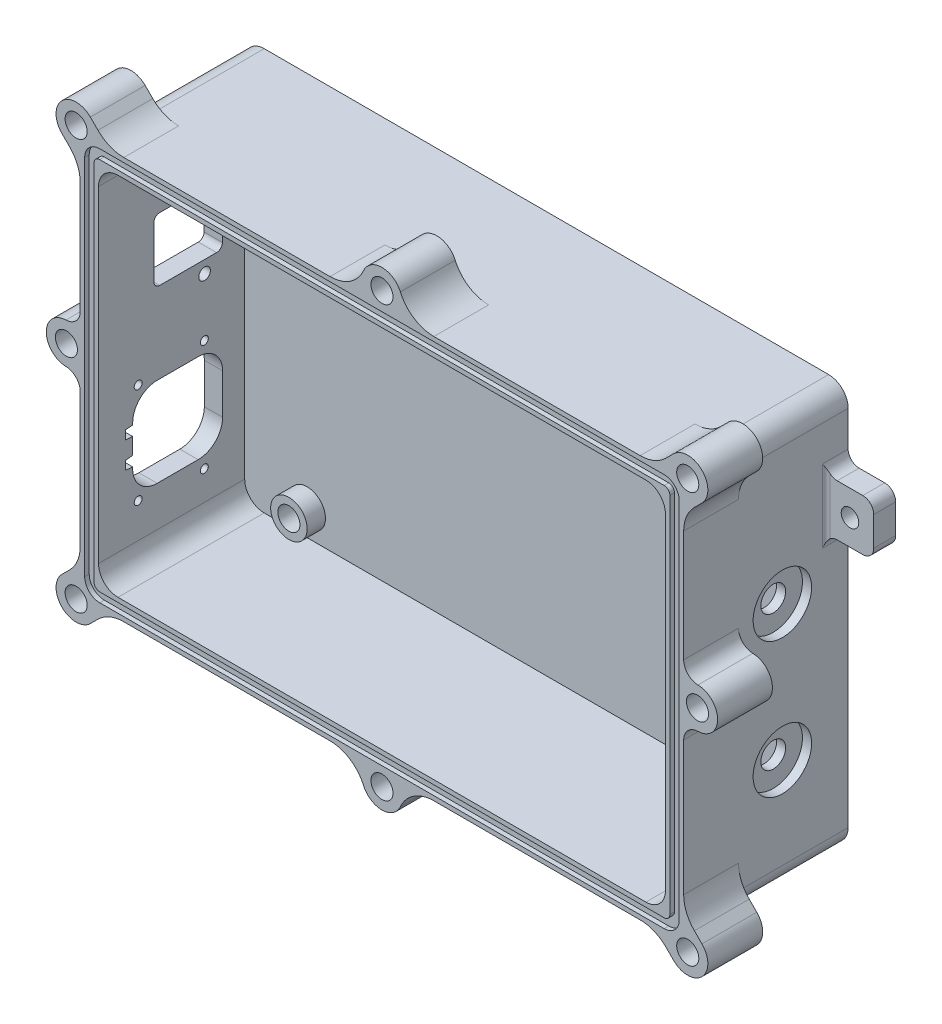
SolidWorks part; units mm, degrees
material "Custom Plastic"
ref_plane "X-Y Datum" through (0, 0, 0) normal (0, 0, 1) x (1, 0, 0)
ref_plane "X-Z Datum" through (0, 0, 0) normal (0, 1, 0) x (1, 0, 0)
ref_plane "Y-Z Datum" through (0, 0, 0) normal (1, 0, 0) x (0, 0, -1)
sketch "Sketch1" plane through (0, 0, 0) normal (0, 0, 1) x (1, 0, 0)
  line L1 (-82.55, 55) -> (82.55, 55)
  line L2 (-82.55, 55) -> (-82.55, -55)
  line L3 (-82.55, -55) -> (82.55, -55)
  line L4 (82.55, 55) -> (82.55, -55)
  line L5 (-82.55, 55) -> (82.55, -55) construction
  line L6 (-82.55, -55) -> (82.55, 55) construction
  point P0 (0, 0)
  dimension "D1" = 165.1
  dimension "D2" = 110
extrude "Boss-Extrude1" add sketch "Sketch1" along normal blind 45
shell "Shell1" thickness 5 removed face at (0, 0, 45)
fillet "Fillet1" radius 5.334 8 edges at (-77.55, -50, 25) (-82.55, -55, 22.5) (82.55, -55, 22.5) (77.55, -50, 25) (82.55, 55, 22.5) (77.55, 50, 25) (-82.55, 55, 22.5) (-77.55, 50, 25)
sketch "Sketch2" plane through (0, 0, 45) normal (0, 0, 1) x (1, 0, 0)
  line L20 (-77.216, -53.7827) -> (77.216, -53.7827)
  line L21 (81.3327, -49.666) -> (81.3327, 49.666)
  line L22 (77.216, 53.7827) -> (-77.216, 53.7827)
  line L23 (-81.3327, 49.666) -> (-81.3327, -49.666)
  line L24 (-77.216, -52.5) -> (77.216, -52.5)
  line L25 (80.05, -49.666) -> (80.05, 49.666)
  line L26 (77.216, 52.5) -> (-77.216, 52.5)
  line L27 (-80.05, 49.666) -> (-80.05, -49.666)
  line L28 (-77.216, -52.5) -> (77.216, -52.5) construction
  line L29 (80.05, -49.666) -> (80.05, 49.666) construction
  line L30 (77.216, 52.5) -> (-77.216, 52.5) construction
  line L31 (-80.05, 49.666) -> (-80.05, -49.666) construction
  line L32 (-78.7673, 49.666) -> (-78.7673, -49.666)
  line L33 (-77.216, -51.2173) -> (77.216, -51.2173)
  line L34 (78.7673, -49.666) -> (78.7673, 49.666)
  line L35 (77.216, 51.2173) -> (-77.216, 51.2173)
  arc A16 (77.216, -53.7827) -> (81.3327, -49.666) centre (77.216, -49.666) ccw
  arc A17 (81.3327, 49.666) -> (77.216, 53.7827) centre (77.216, 49.666) ccw
  arc A18 (-77.216, 53.7827) -> (-81.3327, 49.666) centre (-77.216, 49.666) ccw
  arc A19 (-81.3327, -49.666) -> (-77.216, -53.7827) centre (-77.216, -49.666) ccw
  arc A20 (-80.05, -49.666) -> (-77.216, -52.5) centre (-77.216, -49.666) ccw
  arc A21 (77.216, -52.5) -> (80.05, -49.666) centre (77.216, -49.666) ccw
  arc A22 (80.05, 49.666) -> (77.216, 52.5) centre (77.216, 49.666) ccw
  arc A23 (-77.216, 52.5) -> (-80.05, 49.666) centre (-77.216, 49.666) ccw
  arc A24 (-80.05, -49.666) -> (-77.216, -52.5) centre (-77.216, -49.666) ccw construction
  arc A25 (77.216, -52.5) -> (80.05, -49.666) centre (77.216, -49.666) ccw construction
  arc A26 (80.05, 49.666) -> (77.216, 52.5) centre (77.216, 49.666) ccw construction
  arc A27 (-77.216, 52.5) -> (-80.05, 49.666) centre (-77.216, 49.666) ccw construction
  arc A28 (-77.216, 51.2173) -> (-78.7673, 49.666) centre (-77.216, 49.666) ccw
  arc A29 (-78.7673, -49.666) -> (-77.216, -51.2173) centre (-77.216, -49.666) ccw
  arc A30 (77.216, -51.2173) -> (78.7673, -49.666) centre (77.216, -49.666) ccw
  arc A31 (78.7673, 49.666) -> (77.216, 51.2173) centre (77.216, 49.666) ccw
  dimension "D1" = 2.5
  dimension "D2" = 1.2827
  dimension "D3" = 1.2827
extrude "Cut-Extrude1" cut sketch "Sketch2" against normal blind 1.2446
sketch "Sketch3" plane through (0, 0, 45) normal (0, 0, 1) x (1, 0, 0)
  line L0 (77.216, 49.666) -> (80.9877, 53.4377)
  line L1 (80.9877, 53.4377) -> (83.6625, 56.1125)
  line L2 (79.7734, 60.0016) -> (74.7718, 55)
  line L3 (77.216, 55) -> (-77.216, 55) construction
  line L4 (82.55, -49.666) -> (82.55, 49.666) construction
  line L5 (82.55, -49.666) -> (82.55, 49.666)
  line L6 (77.216, 55) -> (-77.216, 55)
  line L7 (87.5516, 52.2234) -> (82.55, 47.2218)
  arc A0 (82.55, 49.666) -> (77.216, 55) centre (77.216, 49.666) ccw construction
  circle A1 centre (83.6625, 56.1125) radius 3.025
  circle A2 centre (83.6625, 56.1125) radius 5.5
  arc A3 (81.3327, 49.666) -> (77.216, 53.7827) centre (77.216, 49.666) ccw construction
  arc A4 (82.55, 49.666) -> (77.216, 55) centre (77.216, 49.666) ccw
  point P10 (80.1269, 52.5769)
  arc M15 (82.55, 49.666) -> (77.216, 55) centre (77.216, 49.666) ccw
  line M16 (77.216, 55) -> (-77.216, 55)
  dimension "D1" = 6.05
  dimension "D2" = 11
  dimension "D3" = 5
extrude "Boss-Extrude2" add sketch "Sketch3" against normal blind 15 contours A2 L5 L7 M15 | A2 A1 M15 | A2 L2 M16 M15 | A1 region at (82.5376, 58.8282, 45) region at (79.824, 54.4965, 45) region at (77.1925, 56.331, 45) region at (83.881, 49.6425, 45)
sketch "Sketch4" plane through (0, 0, 45) normal (0, 0, 1) x (1, 0, 0)
  line L0 (87.5516, 52.2234) -> (82.55, 47.2218) construction
  line L1 (79.7734, 60.0016) -> (74.7718, 55) construction
  line L2 (77.216, 49.666) -> (80.9877, 53.4377) construction
  line L3 (80.9877, 53.4377) -> (83.6625, 56.1125) construction
  line L4 (82.55, -49.666) -> (82.55, 49.666) construction
  line L5 (77.216, 55) -> (-77.216, 55) construction
  line L6 (87.5516, 52.2234) -> (82.55, 47.2218)
  line L7 (79.7734, 60.0016) -> (74.7718, 55)
  line L8 (77.216, 49.666) -> (80.9877, 53.4377)
  line L9 (80.9877, 53.4377) -> (83.6625, 56.1125)
  line L10 (82.55, -49.666) -> (82.55, 49.666)
  line L11 (77.216, 55) -> (-77.216, 55)
  arc A0 (82.55, 49.666) -> (77.216, 55) centre (77.216, 49.666) ccw construction
  circle A1 centre (83.6625, 56.1125) radius 5.5
  circle A2 centre (83.6625, 56.1125) radius 5.5
  circle A3 centre (83.6625, 56.1125) radius 3.025
  circle A4 centre (83.6625, 56.1125) radius 3.025
  arc A5 (82.55, 49.666) -> (77.216, 55) centre (77.216, 49.666) ccw
  dimension "D1" = 0
  dimension "D2" = 0
extrude "Cut-Extrude2" cut sketch "Sketch4" against normal blind 8 contours A4 region at (82.5376, 58.8282, 45)
mirror "Mirror2" about plane through (0, 0, 0) normal (0, 1, 0) of "Cut-Extrude2", "Boss-Extrude2"
mirror "Mirror3" about plane through (0, 0, 0) normal (1, 0, 0) of "Mirror2"
fillet "Fillet3" radius 10 8 edges at (82.55, 47.2218, 37.5) (74.7718, 55, 37.5) (-74.7718, 55, 37.5) (-82.55, 47.2218, 37.5) (-82.55, -47.2218, 37.5) (-74.7718, -55, 37.5) (74.7718, -55, 37.5) (82.55, -47.2218, 37.5)
sketch "Sketch5" plane through (0, 0, 45) normal (0, 0, 1) x (1, 0, 0)
  line L1 (0, -55) -> (0, -58.7827)
  line L2 (-70.6297, -55) -> (70.6297, -55) construction
  line L3 (-77.216, -53.7827) -> (77.216, -53.7827) construction
  line L4 (-5.5, -58.7827) -> (-5.5, -55)
  line L5 (5.5, -58.7827) -> (5.5, -55)
  line L6 (-70.6297, -55) -> (70.6297, -55)
  circle A0 centre (0, -58.7827) radius 3.025
  circle A1 centre (0, -58.7827) radius 5.5
  line M18 (-70.6297, -55) -> (70.6297, -55)
  dimension "D1" = 6.05
  dimension "D2" = 11
  dimension "D3" = 5
extrude "Boss-Extrude3" add sketch "Sketch5" against normal blind 15 contours A0 | A1 A0 L6 M18 | A1 L5 L6 | A1 L4 M18 region at (2.0785, -56.7042, 45) region at (1.9963, -55.1439, 45) region at (-5.0608, -55.9178, 45) region at (5.0608, -55.9178, 45)
sketch "Sketch6" plane through (0, 0, 45) normal (0, 0, 1) x (1, 0, 0)
  line L0 (-70.6297, -55) -> (70.6297, -55) construction
  line L1 (5.5, -58.7827) -> (5.5, -55) construction
  line L2 (-5.5, -58.7827) -> (-5.5, -55) construction
  line L3 (0, -55) -> (0, -58.7827) construction
  line L4 (-70.6297, -55) -> (70.6297, -55)
  line L5 (5.5, -58.7827) -> (5.5, -55)
  line L6 (-5.5, -58.7827) -> (-5.5, -55)
  line L7 (0, -55) -> (0, -58.7827)
  circle A1 centre (0, -58.7827) radius 5.5
  circle A2 centre (0, -58.7827) radius 5.5
  circle A3 centre (0, -58.7827) radius 3.025
  circle A4 centre (0, -58.7827) radius 3.025
  dimension "D1" = 0
  dimension "D2" = 0
extrude "Cut-Extrude3" cut sketch "Sketch6" against normal blind 8 contours A4 region at (2.0785, -56.7042, 45)
mirror "Mirror10" about plane through (0, 0, 0) normal (0, 1, 0) of "Cut-Extrude3", "Boss-Extrude3"
fillet "Fillet5" radius 10 4 edges at (5.5, 55, 37.5) (-5.5, 55, 37.5) (-5.5, -55, 37.5) (5.5, -55, 37.5)
sketch "Sketch7" plane through (0, 0, 45) normal (0, 0, 1) x (1, 0, 0)
  line L0 (-82.55, 3.0797) -> (-86.3327, 3.0797)
  line L2 (-82.55, 43.0797) -> (-82.55, -43.0797) construction
  line L3 (-81.3327, 49.666) -> (-81.3327, -49.666) construction
  line L4 (-86.3327, 8.5797) -> (-82.55, 8.5797)
  line L5 (-86.3327, -2.4203) -> (-82.55, -2.4203)
  line L6 (-82.55, 43.0797) -> (-82.55, -43.0797)
  circle A0 centre (-86.3327, 3.0797) radius 3.025
  circle A1 centre (-86.3327, 3.0797) radius 5.5
  line M18 (-82.55, 43.0797) -> (-82.55, -43.0797)
  dimension "D1" = 6.05
  dimension "D2" = 11
  dimension "D3" = 5
  dimension "D4" = 40
extrude "Boss-Extrude4" add sketch "Sketch7" against normal blind 15 contours A1 L4 M18 | A1 L5 L6 | L6 A1 A0 M18 | A0 region at (-89.2721, 3.0797, 45) region at (-82.6939, 1.0834, 45) region at (-83.4678, 8.1405, 45) region at (-83.4678, -1.9811, 45)
sketch "Sketch8" plane through (0, 0, 45) normal (0, 0, 1) x (1, 0, 0)
  line L0 (-78.7673, 49.666) -> (-78.7673, -49.666) construction
  line L1 (-82.55, 43.0797) -> (-82.55, -43.0797) construction
  line L2 (-86.3327, -2.4203) -> (-82.55, -2.4203) construction
  line L3 (-86.3327, 8.5797) -> (-82.55, 8.5797) construction
  line L4 (-82.55, 3.0797) -> (-86.3327, 3.0797) construction
  line L5 (-82.55, 43.0797) -> (-82.55, -43.0797)
  line L6 (-86.3327, -2.4203) -> (-82.55, -2.4203)
  line L7 (-86.3327, 8.5797) -> (-82.55, 8.5797)
  line L8 (-82.55, 3.0797) -> (-86.3327, 3.0797)
  circle A1 centre (-86.3327, 3.0797) radius 5.5
  circle A2 centre (-86.3327, 3.0797) radius 5.5
  circle A3 centre (-86.3327, 3.0797) radius 3.025
  circle A4 centre (-86.3327, 3.0797) radius 3.025
  point P0 (-78.7673, 0)
  dimension "D1" = 0
  dimension "D2" = 0
extrude "Cut-Extrude4" cut sketch "Sketch8" against normal blind 8 contours A4 region at (-89.2721, 3.0797, 45)
mirror "Mirror11" about plane through (0, 0, 0) normal (1, 0, 0) of "Cut-Extrude4", "Boss-Extrude4"
fillet "Fillet6" radius 4 4 edges at (82.55, 8.5797, 37.5) (82.55, -2.4203, 37.5) (-82.55, 8.5797, 37.5) (-82.55, -2.4203, 37.5)
sketch "Sketch9" plane through (0, 0, 5) normal (0, 0, 1) x (1, 0, 0)
  circle A0 centre (-60.455, 42.799) radius 3.025
  circle A1 centre (50.035, 12.954) radius 3.025
  circle A2 centre (50.035, -42.926) radius 3.025
  circle A3 centre (-60.455, -42.926) radius 3.025
  circle A4 centre (-60.455, -42.926) radius 5
  circle A5 centre (50.035, -42.926) radius 5
  circle A6 centre (50.035, 12.954) radius 5
  circle A7 centre (-60.455, 42.799) radius 5
  point P0 (-60.455, 42.799)
  point P1 (50.035, 12.954)
  point P3 (50.035, -42.926)
  point P5 (-60.455, -42.926)
  dimension "D1" = 6.05
  dimension "D2" = 10
extrude "Boss-Extrude5" add sketch "Sketch9" along normal blind 5
sketch "Sketch10" plane through (0, 0, 0) normal (0, 0, -1) x (-1, 0, 0)
  line L0 (70.6297, -55) -> (14.1984, -55) construction
  line L1 (50.55, -55) -> (64.55, -55)
  line L2 (50.55, -55) -> (50.55, -68)
  line L3 (50.55, -68) -> (64.55, -68)
  line L4 (64.55, -55) -> (64.55, -68)
  line L15 (-82.55, 12.5772) -> (-82.55, 43.0797) construction
  line L16 (-82.55, 37) -> (-95.55, 37)
  line L17 (-82.55, 37) -> (-82.55, 23)
  line L18 (-82.55, 23) -> (-95.55, 23)
  line L19 (-95.55, 37) -> (-95.55, 23)
  line L20 (-95.55, 23) -> (-82.55, 37) construction
  line L21 (50.55, -68) -> (64.55, -55) construction
  line L22 (-70.6297, 55) -> (-14.1984, 55) construction
  line L23 (82.55, -6.4178) -> (82.55, -43.0797) construction
  circle A0 centre (-89.05, 30) radius 2 construction
  circle A1 centre (57.55, -61.5) radius 2 construction
  dimension "D1" = 4
  dimension "D4" = 4
  dimension "D2" = 14
  dimension "D3" = 13
  dimension "D5" = 25
  dimension "D6" = 25
extrude "Boss-Extrude6" add sketch "Sketch10" against normal blind 6
hole_wizard "M4 Clearance Hole1" positions "Sketch13" profile "Sketch12" hole size "M4" standard "ANSI Metric" end condition through all
sketch "Sketch13" plane through (0, 0, 6) normal (0, 0, 1) x (1, 0, 0)
  point P0 (-57.55, -61.5)
  point P3 (89.05, 30)
sketch "Sketch12" plane through (-57.55, -61.5, 6) normal (1, 0, 0) x (0, -1, 0)
  line L0 (0, 0) -> (0, 6)
  line L1 (0, 6) -> (2.4, 6)
  line L2 (2.4, 6) -> (2.4, 0)
  line L5 (2.4, 0) -> (0, 0)
  line L11 (0, -6.35) -> (0, 107.95) construction
  dimension "Thru Hole Dia." = 4.8
  dimension "Thru Hole Depth" = 6
fillet "Fillet7" radius 3 8 edges at (-50.55, -55, 3) (-64.55, -55, 3) (-64.55, -68, 3) (-50.55, -68, 3) (95.55, 37, 3) (95.55, 23, 3) (82.55, 23, 3) (82.55, 37, 3)
fillet "Fillet8" radius 1 2 edges at (-57.55, -55, 6) (82.55, 30, 6)
sketch "Sketch14" plane through (-82.55, 0, 0) normal (-1, 0, 0) x (0, 0, 1)
  line L0 (37.1425, -18.606) -> (37.1425, -17.1559) construction
  line L1 (37.1425, -25.806) -> (37.1425, -24.3559) construction
  line L2 (28.9425, -9.781) -> (17.7425, -9.781) construction
  line L3 (11.5425, -15.981) -> (11.5425, -26.981) construction
  line L4 (17.7425, -33.181) -> (28.9425, -33.181) construction
  line L5 (35.1425, -26.981) -> (35.1425, -25.981) construction
  line L6 (35.282, -25.9688) -> (37.1425, -25.806) construction
  line L7 (34.837, -26.0077) -> (35.282, -25.9688) construction
  line L8 (35.282, -24.1931) -> (37.1425, -24.3559) construction
  line L9 (35.1425, -24.181) -> (35.1425, -18.781) construction
  line L10 (34.837, -18.8077) -> (35.282, -18.7688) construction
  line L11 (35.282, -18.7688) -> (37.1425, -18.606) construction
  line L12 (35.282, -16.9931) -> (37.1425, -17.1559) construction
  line L13 (35.1425, -16.981) -> (35.1425, -15.981) construction
  line L14 (37.1425, -18.606) -> (37.1425, -17.1559) construction
  line L15 (37.1425, -25.806) -> (37.1425, -24.3559) construction
  line L16 (28.9425, -9.781) -> (17.7425, -9.781) construction
  line L17 (11.5425, -15.981) -> (11.5425, -26.981) construction
  line L18 (17.7425, -33.181) -> (28.9425, -33.181) construction
  line L19 (35.1425, -26.981) -> (35.1425, -25.981) construction
  line L20 (35.282, -25.9688) -> (37.1425, -25.806) construction
  line L21 (34.837, -26.0077) -> (35.282, -25.9688) construction
  line L22 (35.282, -24.1931) -> (37.1425, -24.3559) construction
  line L23 (35.1425, -24.181) -> (35.1425, -18.781) construction
  line L24 (34.837, -18.8077) -> (35.282, -18.7688) construction
  line L25 (35.282, -18.7688) -> (37.1425, -18.606) construction
  line L26 (35.282, -16.9931) -> (37.1425, -17.1559) construction
  line L27 (35.1425, -16.981) -> (35.1425, -15.981) construction
  line L28 (34.8806, -19.3058) -> (35.3255, -19.2669)
  line L29 (35.3255, -19.2669) -> (37.6425, -19.0641)
  line L30 (37.6425, -19.0641) -> (37.6425, -16.6978)
  line L31 (35.3264, -16.4951) -> (37.6425, -16.6978)
  line L32 (34.8806, -26.5058) -> (35.3255, -26.4669)
  line L33 (35.3255, -26.4669) -> (37.6425, -26.2641)
  line L34 (37.6425, -26.2641) -> (37.6425, -23.8978)
  line L35 (35.3264, -23.6951) -> (37.6425, -23.8978)
  line L36 (35.6425, -16.981) -> (35.6425, -15.981)
  line L37 (28.9425, -9.281) -> (17.7425, -9.281)
  line L38 (11.0425, -15.981) -> (11.0425, -26.981)
  line L39 (17.7425, -33.681) -> (28.9425, -33.681)
  line L40 (35.6425, -26.981) -> (35.6425, -25.981)
  line L41 (35.6425, -24.181) -> (35.6425, -18.781)
  line L42 (28.2478, 29.611) -> (12.6978, 29.611) construction
  line L43 (11.5978, 28.511) -> (11.5978, 14.461) construction
  line L44 (12.6978, 13.361) -> (28.2478, 13.361) construction
  line L45 (29.3478, 14.461) -> (29.3478, 28.511) construction
  line L46 (28.2478, 29.611) -> (12.6978, 29.611) construction
  line L47 (11.5978, 28.511) -> (11.5978, 14.461) construction
  line L48 (12.6978, 13.361) -> (28.2478, 13.361) construction
  line L49 (29.3478, 14.461) -> (29.3478, 28.511) construction
  line L50 (16.9728, 9.486) -> (14.9728, 9.486) construction
  line L51 (25.9728, 33.486) -> (23.9728, 33.486) construction
  line L52 (28.2478, 30.111) -> (12.6978, 30.111)
  line L53 (11.0978, 28.511) -> (11.0978, 14.461)
  line L54 (12.6978, 12.861) -> (28.2478, 12.861)
  line L55 (29.8478, 14.461) -> (29.8478, 28.511)
  spline S0 degree 3 poles (17.7425, -9.781) (14.1107, -9.781) (11.5425, -12.3491) (11.5425, -15.981) knots 0 0 0 0 1 1 1 1 weights 1 0.804738 0.804738 1 construction
  spline S1 degree 3 poles (11.5425, -26.981) (11.5425, -30.6128) (14.1107, -33.181) (17.7425, -33.181) knots 0 0 0 0 1 1 1 1 weights 1 0.804738 0.804738 1 construction
  spline S2 degree 3 poles (28.9425, -33.181) (32.5744, -33.181) (35.1425, -30.6128) (35.1425, -26.981) knots 0 0 0 0 1 1 1 1 weights 1 0.804738 0.804738 1 construction
  spline S3 degree 3 poles (2026.1511, -214.6767) (16.8817, -22.4202) (37.0242, -24.3539) (35.1725, -24.1831) (35.0836, -24.1753) (30.4685, -23.7841) (6.3657, -21.3606) (2023.9813, -231.7948) knots -14.295266 -14.295266 -14.295266 -14.295266 0.151076 0.326628 0.526648 0.751115 27.466708 27.466708 27.466708 27.466708 only from (35.282, -24.1931) to (34.837, -24.1542) construction
  spline S4 degree 3 poles (2026.1511, -207.4767) (16.8817, -15.2202) (37.0242, -17.1539) (35.1725, -16.9831) (35.0836, -16.9753) (30.4685, -16.5841) (6.3657, -14.1606) (2023.9813, -224.5948) knots -14.295266 -14.295266 -14.295266 -14.295266 0.151076 0.326628 0.526648 0.751115 27.466708 27.466708 27.466708 27.466708 only from (35.282, -16.9931) to (34.837, -16.9542) construction
  spline S5 degree 3 poles (35.1425, -15.981) (35.1425, -12.3491) (32.5744, -9.781) (28.9425, -9.781) knots 0 0 0 0 1 1 1 1 weights 1 0.804738 0.804738 1 construction
  spline S6 degree 3 poles (17.7425, -9.781) (14.1107, -9.781) (11.5425, -12.3491) (11.5425, -15.981) knots 0 0 0 0 1 1 1 1 weights 1 0.804738 0.804738 1 construction
  spline S7 degree 3 poles (11.5425, -26.981) (11.5425, -30.6128) (14.1107, -33.181) (17.7425, -33.181) knots 0 0 0 0 1 1 1 1 weights 1 0.804738 0.804738 1 construction
  spline S8 degree 3 poles (28.9425, -33.181) (32.5744, -33.181) (35.1425, -30.6128) (35.1425, -26.981) knots 0 0 0 0 1 1 1 1 weights 1 0.804738 0.804738 1 construction
  spline S9 degree 3 poles (35.282, -24.1931) (35.2682, -24.1919) (35.2383, -24.1892) (35.1725, -24.1831) (35.0836, -24.1753) (34.9691, -24.1656) (34.8825, -24.1581) (34.837, -24.1542) knots 0 0 0 0 0.151076 0.326628 0.526648 0.751115 1 1 1 1 construction
  spline S10 degree 3 poles (35.282, -16.9931) (35.2682, -16.9919) (35.2383, -16.9892) (35.1725, -16.9831) (35.0836, -16.9753) (34.9691, -16.9656) (34.8825, -16.9581) (34.837, -16.9542) knots 0 0 0 0 0.151076 0.326628 0.526648 0.751115 1 1 1 1 construction
  spline S11 degree 3 poles (35.1425, -15.981) (35.1425, -12.3491) (32.5744, -9.781) (28.9425, -9.781) knots 0 0 0 0 1 1 1 1 weights 1 0.804738 0.804738 1 construction
  spline S12 degree 1 poles (35.3264, -16.4951) (34.8799, -16.4561) knots 0 0 1 1 construction
  spline S13 degree 3 poles (35.3264, -16.4951) (35.3004, -16.4928) (35.2564, -16.4887) (35.1419, -16.4784) (35.0167, -16.4678) (34.9248, -16.4599) (34.8799, -16.4561) knots 0.00312 0.00312 0.00312 0.00312 0.25234 0.50156 0.75078 1 1 1 1
  spline S14 degree 1 poles (35.3264, -23.6951) (34.8799, -23.6561) knots 0 0 1 1 construction
  spline S15 degree 3 poles (35.3264, -23.6951) (35.3004, -23.6928) (35.2564, -23.6887) (35.1419, -23.6784) (35.0167, -23.6678) (34.9248, -23.6599) (34.8799, -23.6561) knots 0.00312 0.00312 0.00312 0.00312 0.25234 0.50156 0.75078 1 1 1 1
  spline S16 degree 1 poles (35.6425, -15.981) (28.9425, -9.281) knots 0 0 1 1 construction
  spline S17 degree 1 poles (17.7425, -9.281) (11.0425, -15.981) knots 0 0 1 1 construction
  spline S18 degree 1 poles (11.0425, -26.981) (17.7425, -33.681) knots 0 0 1 1 construction
  spline S19 degree 1 poles (28.9425, -33.681) (35.6425, -26.981) knots 0 0 1 1 construction
  spline S20 degree 3 poles (35.6425, -15.981) (35.6425, -15.5729) (35.5721, -14.773) (35.1002, -13.0836) (33.8203, -11.1032) (31.8399, -9.8233) (30.1505, -9.3514) (29.3506, -9.281) (28.9425, -9.281) knots 0 0 0 0 0.125 0.25 0.5 0.75 0.875 1 1 1 1
  spline S21 degree 3 poles (17.7425, -9.281) (17.3345, -9.281) (16.5346, -9.3514) (14.8452, -9.8233) (12.8648, -11.1032) (11.5849, -13.0836) (11.113, -14.773) (11.0425, -15.5729) (11.0425, -15.981) knots 0 0 0 0 0.125 0.25 0.5 0.75 0.875 1 1 1 1
  spline S22 degree 3 poles (11.0425, -26.981) (11.0425, -27.389) (11.113, -28.1889) (11.5849, -29.8783) (12.8648, -31.8587) (14.8452, -33.1386) (16.5346, -33.6105) (17.3345, -33.681) (17.7425, -33.681) knots 0 0 0 0 0.125 0.25 0.5 0.75 0.875 1 1 1 1
  spline S23 degree 3 poles (28.9425, -33.681) (29.3506, -33.681) (30.1505, -33.6105) (31.8399, -33.1386) (33.8203, -31.8587) (35.1002, -29.8783) (35.5721, -28.1889) (35.6425, -27.389) (35.6425, -26.981) knots 0 0 0 0 0.125 0.25 0.5 0.75 0.875 1 1 1 1
  spline S24 degree 3 poles (23.9728, 33.486) (23.9728, 31.486) (25.9728, 31.486) (25.9728, 33.486) knots 0 0 0 0 1 1 1 1 weights 1 0.333333 0.333333 1 construction
  spline S25 degree 3 poles (25.9728, 33.486) (25.9728, 35.486) (23.9728, 35.486) (23.9728, 33.486) knots 0 0 0 0 1 1 1 1 weights 1 0.333333 0.333333 1 construction
  spline S26 degree 3 poles (23.9728, 33.486) (23.9728, 31.486) (25.9728, 31.486) (25.9728, 33.486) knots 0 0 0 0 1 1 1 1 weights 1 0.333333 0.333333 1 construction
  spline S27 degree 3 poles (25.9728, 33.486) (25.9728, 35.486) (23.9728, 35.486) (23.9728, 33.486) knots 0 0 0 0 1 1 1 1 weights 1 0.333333 0.333333 1 construction
  spline S28 degree 3 poles (16.9728, 9.486) (16.9728, 11.486) (14.9728, 11.486) (14.9728, 9.486) knots 0 0 0 0 1 1 1 1 weights 1 0.333333 0.333333 1 construction
  spline S29 degree 3 poles (14.9728, 9.486) (14.9728, 7.486) (16.9728, 7.486) (16.9728, 9.486) knots 0 0 0 0 1 1 1 1 weights 1 0.333333 0.333333 1 construction
  spline S30 degree 3 poles (16.9728, 9.486) (16.9728, 11.486) (14.9728, 11.486) (14.9728, 9.486) knots 0 0 0 0 1 1 1 1 weights 1 0.333333 0.333333 1 construction
  spline S31 degree 3 poles (14.9728, 9.486) (14.9728, 7.486) (16.9728, 7.486) (16.9728, 9.486) knots 0 0 0 0 1 1 1 1 weights 1 0.333333 0.333333 1 construction
  spline S32 degree 3 poles (34.1425, -36.266) (36.3125, -36.266) (36.3125, -34.096) (34.1425, -34.096) knots 0 0 0 0 1 1 1 1 weights 1 0.333333 0.333333 1 construction
  spline S33 degree 3 poles (34.1425, -34.096) (31.9725, -34.096) (31.9725, -36.266) (34.1425, -36.266) knots 0 0 0 0 1 1 1 1 weights 1 0.333333 0.333333 1 construction
  spline S34 degree 3 poles (16.0425, -37.766) (18.2125, -37.766) (18.2125, -35.596) (16.0425, -35.596) knots 0 0 0 0 1 1 1 1 weights 1 0.333333 0.333333 1 construction
  spline S35 degree 3 poles (16.0425, -35.596) (13.8725, -35.596) (13.8725, -37.766) (16.0425, -37.766) knots 0 0 0 0 1 1 1 1 weights 1 0.333333 0.333333 1 construction
  spline S36 degree 3 poles (34.1425, -8.866) (36.3125, -8.866) (36.3125, -6.696) (34.1425, -6.696) knots 0 0 0 0 1 1 1 1 weights 1 0.333333 0.333333 1 construction
  spline S37 degree 3 poles (34.1425, -6.696) (31.9725, -6.696) (31.9725, -8.866) (34.1425, -8.866) knots 0 0 0 0 1 1 1 1 weights 1 0.333333 0.333333 1 construction
  spline S38 degree 3 poles (16.0425, -7.366) (18.2125, -7.366) (18.2125, -5.196) (16.0425, -5.196) knots 0 0 0 0 1 1 1 1 weights 1 0.333333 0.333333 1 construction
  spline S39 degree 3 poles (16.0425, -5.196) (13.8725, -5.196) (13.8725, -7.366) (16.0425, -7.366) knots 0 0 0 0 1 1 1 1 weights 1 0.333333 0.333333 1 construction
  spline S40 degree 3 poles (34.1425, -36.266) (36.3125, -36.266) (36.3125, -34.096) (34.1425, -34.096) knots 0 0 0 0 1 1 1 1 weights 1 0.333333 0.333333 1
  spline S41 degree 3 poles (34.1425, -34.096) (31.9725, -34.096) (31.9725, -36.266) (34.1425, -36.266) knots 0 0 0 0 1 1 1 1 weights 1 0.333333 0.333333 1
  spline S42 degree 3 poles (16.0425, -37.766) (18.2125, -37.766) (18.2125, -35.596) (16.0425, -35.596) knots 0 0 0 0 1 1 1 1 weights 1 0.333333 0.333333 1
  spline S43 degree 3 poles (16.0425, -35.596) (13.8725, -35.596) (13.8725, -37.766) (16.0425, -37.766) knots 0 0 0 0 1 1 1 1 weights 1 0.333333 0.333333 1
  spline S44 degree 3 poles (34.1425, -8.866) (36.3125, -8.866) (36.3125, -6.696) (34.1425, -6.696) knots 0 0 0 0 1 1 1 1 weights 1 0.333333 0.333333 1
  spline S45 degree 3 poles (34.1425, -6.696) (31.9725, -6.696) (31.9725, -8.866) (34.1425, -8.866) knots 0 0 0 0 1 1 1 1 weights 1 0.333333 0.333333 1
  spline S46 degree 3 poles (16.0425, -7.366) (18.2125, -7.366) (18.2125, -5.196) (16.0425, -5.196) knots 0 0 0 0 1 1 1 1 weights 1 0.333333 0.333333 1
  spline S47 degree 3 poles (16.0425, -5.196) (13.8725, -5.196) (13.8725, -7.366) (16.0425, -7.366) knots 0 0 0 0 1 1 1 1 weights 1 0.333333 0.333333 1
  spline S48 degree 3 poles (11.5978, 28.511) (11.5978, 29.1554) (12.0535, 29.611) (12.6978, 29.611) knots 0 0 0 0 1 1 1 1 weights 1 0.804738 0.804738 1 construction
  spline S49 degree 3 poles (12.6978, 13.361) (12.0535, 13.361) (11.5978, 13.8166) (11.5978, 14.461) knots 0 0 0 0 1 1 1 1 weights 1 0.804738 0.804738 1 construction
  spline S50 degree 3 poles (29.3478, 14.461) (29.3478, 13.8166) (28.8922, 13.361) (28.2478, 13.361) knots 0 0 0 0 1 1 1 1 weights 1 0.804738 0.804738 1 construction
  spline S51 degree 3 poles (28.2478, 29.611) (28.8922, 29.611) (29.3478, 29.1554) (29.3478, 28.511) knots 0 0 0 0 1 1 1 1 weights 1 0.804738 0.804738 1 construction
  spline S52 degree 3 poles (11.5978, 28.511) (11.5978, 29.1554) (12.0535, 29.611) (12.6978, 29.611) knots 0 0 0 0 1 1 1 1 weights 1 0.804738 0.804738 1 construction
  spline S53 degree 3 poles (12.6978, 13.361) (12.0535, 13.361) (11.5978, 13.8166) (11.5978, 14.461) knots 0 0 0 0 1 1 1 1 weights 1 0.804738 0.804738 1 construction
  spline S54 degree 3 poles (29.3478, 14.461) (29.3478, 13.8166) (28.8922, 13.361) (28.2478, 13.361) knots 0 0 0 0 1 1 1 1 weights 1 0.804738 0.804738 1 construction
  spline S55 degree 3 poles (28.2478, 29.611) (28.8922, 29.611) (29.3478, 29.1554) (29.3478, 28.511) knots 0 0 0 0 1 1 1 1 weights 1 0.804738 0.804738 1 construction
  spline S56 degree 1 poles (11.0978, 28.511) (12.6978, 30.111) knots 0 0 1 1 construction
  spline S57 degree 1 poles (12.6978, 12.861) (11.0978, 14.461) knots 0 0 1 1 construction
  spline S58 degree 1 poles (29.8478, 14.461) (28.2478, 12.861) knots 0 0 1 1 construction
  spline S59 degree 1 poles (28.2478, 30.111) (29.8478, 28.511) knots 0 0 1 1 construction
  spline S60 degree 3 poles (12.6978, 30.111) (12.498, 30.111) (12.1071, 30.0423) (11.5312, 29.6776) (11.1666, 29.1017) (11.0978, 28.7109) (11.0978, 28.511) knots 0 0 0 0 0.25 0.5 0.75 1 1 1 1
  spline S61 degree 3 poles (11.0978, 14.461) (11.0978, 14.2611) (11.1666, 13.8703) (11.5312, 13.2944) (12.1071, 12.9297) (12.498, 12.861) (12.6978, 12.861) knots 0 0 0 0 0.25 0.5 0.75 1 1 1 1
  spline S62 degree 3 poles (28.2478, 12.861) (28.4477, 12.861) (28.8385, 12.9297) (29.4144, 13.2944) (29.7791, 13.8703) (29.8478, 14.2611) (29.8478, 14.461) knots 0 0 0 0 0.25 0.5 0.75 1 1 1 1
  spline S63 degree 3 poles (29.8478, 28.511) (29.8478, 28.7109) (29.7791, 29.1017) (29.4144, 29.6776) (28.8385, 30.0423) (28.4477, 30.111) (28.2478, 30.111) knots 0 0 0 0 0.25 0.5 0.75 1 1 1 1
  point P67 (15.9728, 9.486)
  point P69 (24.9728, 33.486)
  line M32 (45, -6.4178) -> (30, -6.4178)
  dimension "D1" = 0.5
  dimension "D2" = 0.5
extrude "Cut-Extrude5" cut sketch "Sketch14" against normal blind 6 contours L55 S63 L52 S60 L53 S61 L54 S62 | L39 S23 L40 L33 L34 L35 L41 L29 L30 L31 L36 S20 L37 S21 L38 S22 | S46 S47 | S45 S44 M32 | S44 S45 M32 | S40 S41 | S42 S43 region at (-82.55, -21.481, 23.5786) region at (-82.55, 21.486, 20.4728) region at (-82.55, -35.181, 34.1425) region at (-82.55, -36.681, 16.0425) region at (-82.55, -7.781, 34.1425) region at (-82.55, -6.281, 16.0425)
hole_wizard "M3 Clearance Hole1" positions "Sketch18" profile "Sketch16" hole size "M3" standard "ANSI Metric"
sketch "Sketch18" plane through (-82.55, 0, 0) normal (-1, 0, 0) x (0, 0, 1)
  point P0 (15.9728, 9.486)
  point P3 (24.9728, 33.486)
sketch "Sketch16" plane through (-82.55, 9.486, 15.9728) normal (0, 1, 0) x (0, 0, 1)
  line L0 (0, 0) -> (0, 6.9614)
  line L1 (0, 6.9614) -> (1.6, 6)
  line L2 (1.6, 6) -> (1.6, 0)
  line L5 (1.6, 0) -> (0, 0)
  line L10 (0, 6.9614) -> (-1.6, 6) construction
  line L11 (0, -6.35) -> (0, 107.95) construction
  dimension "Hole Dia." = 3.2
  dimension "Hole Depth" = 6
  dimension "Drill Angle" = 118
sketch "Sketch19" plane through (82.55, 0, 0) normal (1, 0, 0) x (0, 0, -1)
  line L0 (-18, -49.666) -> (-18, 49.666) construction
  line L1 (-30, -49.666) -> (0, -49.666) construction
  line L2 (0, 49.666) -> (-30, 49.666) construction
  line L3 (0, -49.666) -> (0, 20) construction
  circle A0 centre (-18, -24.666) radius 3.4
  circle A1 centre (-18, 12.334) radius 3.4
  circle A2 centre (-18, -24.666) radius 8
  circle A3 centre (-18, 12.334) radius 8
  dimension "D1" = 6.8
  dimension "D2" = 16
  dimension "D3" = 37
  dimension "D4" = 18
  dimension "D5" = 25
extrude "Cut-Extrude6" cut sketch "Sketch19" against normal blind 6 contours L0 A0 | L0 A1 | A1 L0 | A0 region at (82.55, -24.666, 16.557) region at (82.55, 12.334, 19.443) region at (82.55, 12.334, 16.557)
sketch "Sketch20" plane through (82.55, 0, 0) normal (1, 0, 0) x (0, 0, -1)
  circle A1 centre (-18, 12.334) radius 8
  circle A2 centre (-18, 12.334) radius 8
  circle A3 centre (-18, -24.666) radius 8
  circle A4 centre (-18, -24.666) radius 8
  circle A5 centre (-18, 12.334) radius 3.4
  circle A6 centre (-18, 12.334) radius 3.4
  circle A7 centre (-18, -24.666) radius 3.4
  circle A8 centre (-18, -24.666) radius 3.4
  dimension "D1" = 0
  dimension "D2" = 0
  dimension "D3" = 0
  dimension "D4" = 0
extrude "Cut-Extrude7" cut sketch "Sketch20" against normal blind 2.5
